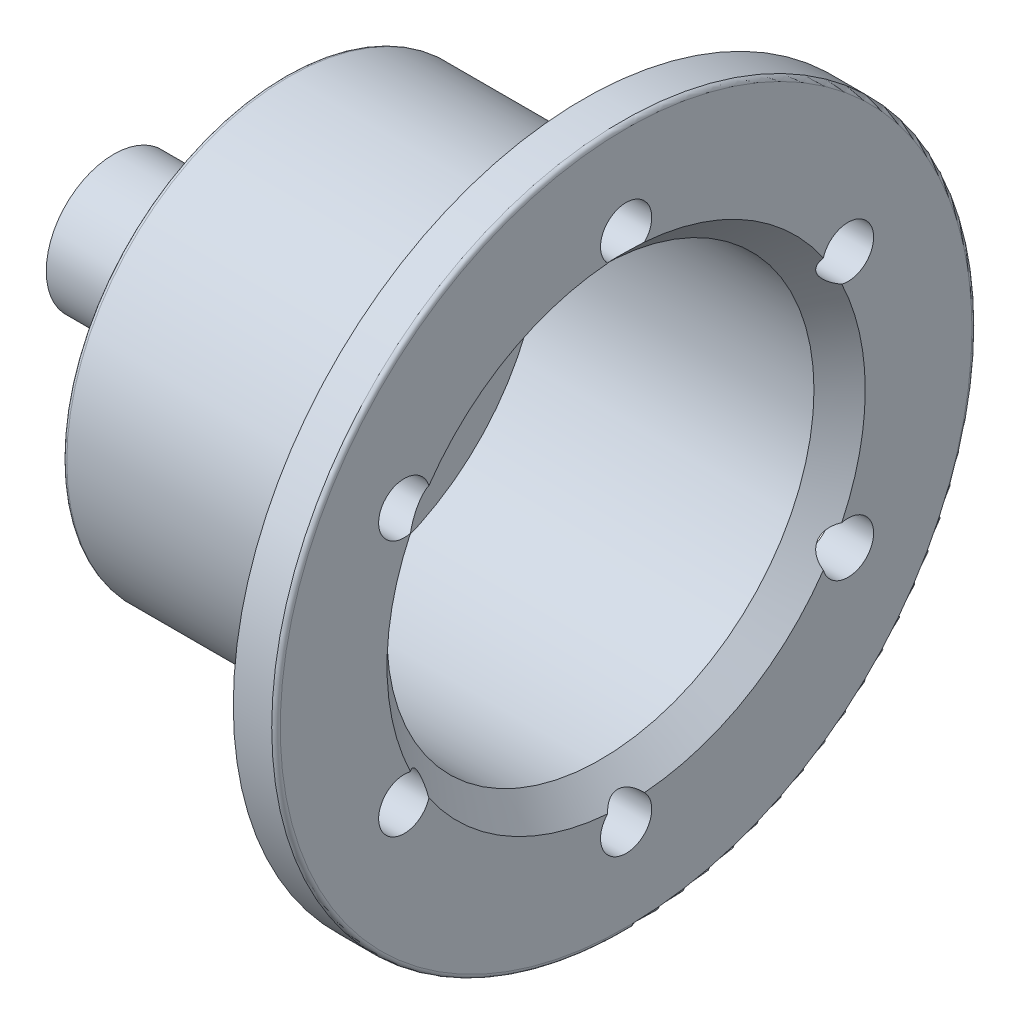
SolidWorks part; units mm, degrees
ref_plane "Front Plane" through (0, 0, 0) normal (0, 0, 1) x (1, 0, 0)
ref_plane "Top Plane" through (0, 0, 0) normal (0, 1, 0) x (1, 0, 0)
ref_plane "Right Plane" through (0, 0, 0) normal (1, 0, 0) x (0, 0, -1)
sketch "Sketch1" plane through (0, 0, 0) normal (1, 0, 0) x (0, 0, -1)
  circle A0 centre (0, 0) radius 30 construction
  circle A1 centre (0, 30) radius 3
  circle A2 centre (25.9808, 15) radius 3
  circle A3 centre (25.9808, -15) radius 3
  circle A4 centre (0, -30) radius 3
  circle A5 centre (-25.9808, -15) radius 3
  circle A6 centre (-25.9808, 15) radius 3
  circle A7 centre (0, 0) radius 41
  point P18 (0, 0)
  dimension "D1" = 60
  dimension "D2" = 6
  dimension "D3" = 82
  dimension "D4" = 6
extrude "Boss-Extrude1" add sketch "Sketch1" along normal blind 40
sketch "Sketch2" plane through (0, 0, 0) normal (-1, 0, 0) x (0, 0, 1)
  circle A0 centre (0, 0) radius 7.9
  dimension "D1" = 15.8
extrude "Boss-Extrude2" add sketch "Sketch2" along normal blind 20 contours A0
fillet "Fillet1" radius 10 1 edges at (0, 0, -7.9)
fillet "Fillet2" radius 0.5 2 edges at (0, 0, -41) (40, 0, -41)
sketch "Sketch3" plane through (0, 0, 0) normal (1, 0, 0) x (0, 0, -1)
  circle A2 centre (0, 0) radius 26
  circle A3 centre (0, 0) radius 57.8383
  dimension "D1" = 52
extrude "Cut-Extrude1" cut sketch "Sketch3" along normal blind 35
fillet "Fillet3" radius 4 1 edges at (35, 0, -26)
fillet "Fillet4" radius 0.5 1 edges at (0, 0, -26)
sketch "Sketch5" plane through (40, 0, 0) normal (1, 0, 0) x (0, 0, -1)
  circle A0 centre (0, 0) radius 25
  dimension "D1" = 50
extrude "Cut-Extrude2" cut sketch "Sketch5" against normal blind 35
chamfer "Chamfer1" distance 3 angle 45 1 edges at (40, 0, -25)
